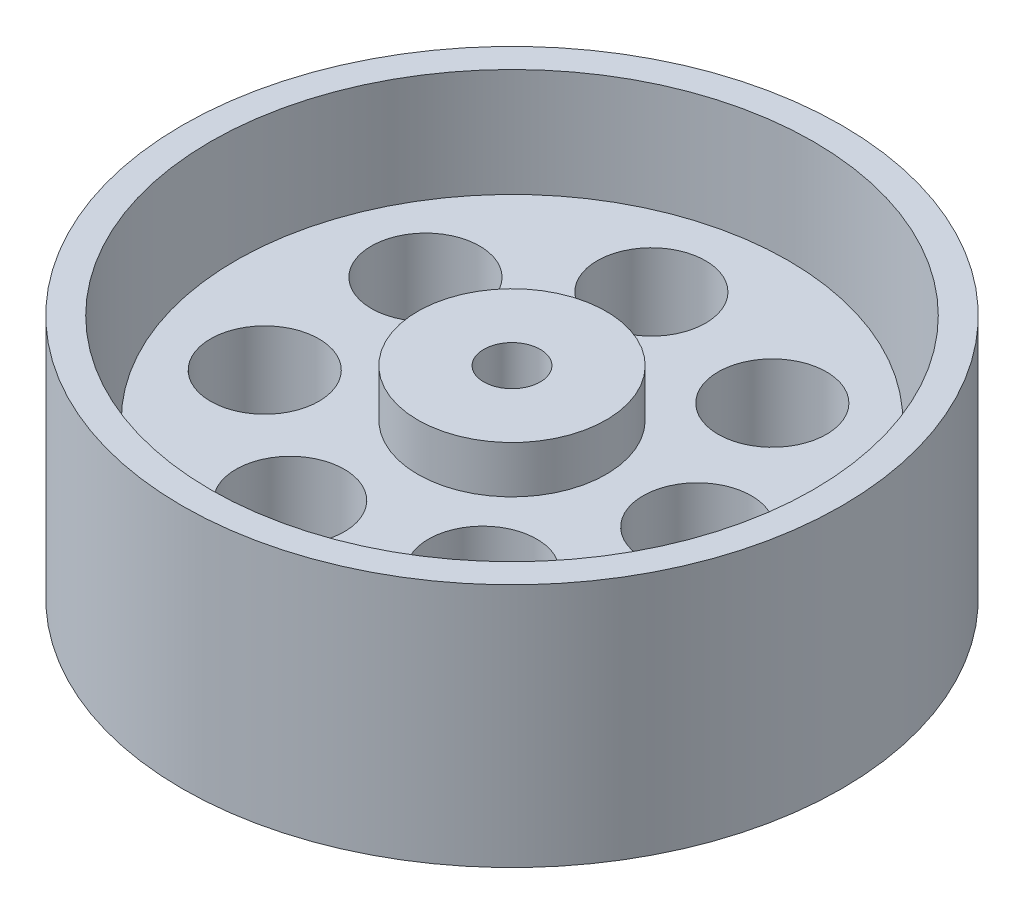
SolidWorks part; units mm, degrees
material "ColorFabb woodFILL"
ref_plane "Front Plane" through (0, 0, 0) normal (0, 0, 1) x (1, 0, 0)
ref_plane "Top Plane" through (0, 0, 0) normal (0, 1, 0) x (1, 0, 0)
ref_plane "Right Plane" through (0, 0, 0) normal (1, 0, 0) x (0, 0, -1)
sketch "Volume Knob" plane through (0, 0, 0) normal (0, 1, 0) x (1, 0, 0)
  line L1 (2.5981, 1.5) -> (-2.5981, 1.5)
  circle A0 centre (0, 0) radius 35
  circle A1 centre (0, 0) radius 20.9
  circle A2 centre (0, 0) radius 32
  circle A3 centre (0, 0) radius 3
  circle A4 centre (0, 0) radius 5.5
  circle A5 centre (0, 0) radius 27.5
  circle A6 centre (0, 0) radius 29.33
  circle A7 centre (0, 0) radius 10
  point P11 (0, 1)
  point P12 (0, 1.5)
extrude "Knob Top" add sketch "Volume Knob" along normal blind 3.5 contours A0
extrude "Knob Walls" add sketch "Volume Knob<3>" along normal blind 26 contours A0 | A2
sketch "Volume Knob<3>" plane through (0, 0, 0) normal (0, 1, 0) x (1, 0, 0) same geometry as "Volume Knob"
extrude "Knob Shaft Keyway" add sketch "Volume Knob<4>" along normal blind 10 from surface contours L1 A3 region at (0, 0, -2.1151) starting at face at (0, 3.5, 32)
sketch "Volume Knob<4>" plane through (0, 0, 0) normal (0, 1, 0) x (1, 0, 0) same geometry as "Volume Knob"
extrude "Knob Damepning Extension (top)" add sketch "Volume Knob<8>" along normal blind 12.9 from surface contours A6 | A3 starting at face at (0, 3.5, 32)
sketch "Volume Knob<8>" plane through (0, 0, 0) normal (0, 1, 0) x (1, 0, 0) same geometry as "Volume Knob"
extrude "Knob Shaft Support" add sketch "Volume Knob<11>" along normal blind 5 from surface contours A3 | A7 starting at face at (0, 16.4, 29.33)
sketch "Volume Knob<11>" plane through (0, 0, 0) normal (0, 1, 0) x (1, 0, 0) same geometry as "Volume Knob"
ref_plane "Plane1" through (0, 16.4, 0) normal (0, 1, 0) x (1, 0, 0)
sketch "Sketch1" plane through (0, 16.4, 0) normal (0, 1, 0) x (1, 0, 0)
  circle A2 centre (19.665, 0) radius 5.75
  circle A3 centre (12.2609, -15.3747) radius 5.75
  circle A4 centre (-4.3759, -19.172) radius 5.75
  circle A5 centre (-17.7176, -8.5323) radius 5.75
  circle A6 centre (-17.7176, 8.5323) radius 5.75
  circle A7 centre (-4.3759, 19.172) radius 5.75
  circle A8 centre (12.2609, 15.3747) radius 5.75
  point P22 (0, 0)
  dimension "D1" = 7
extrude "Weight Slug Holes" cut sketch "Sketch1" against normal blind 12.7
